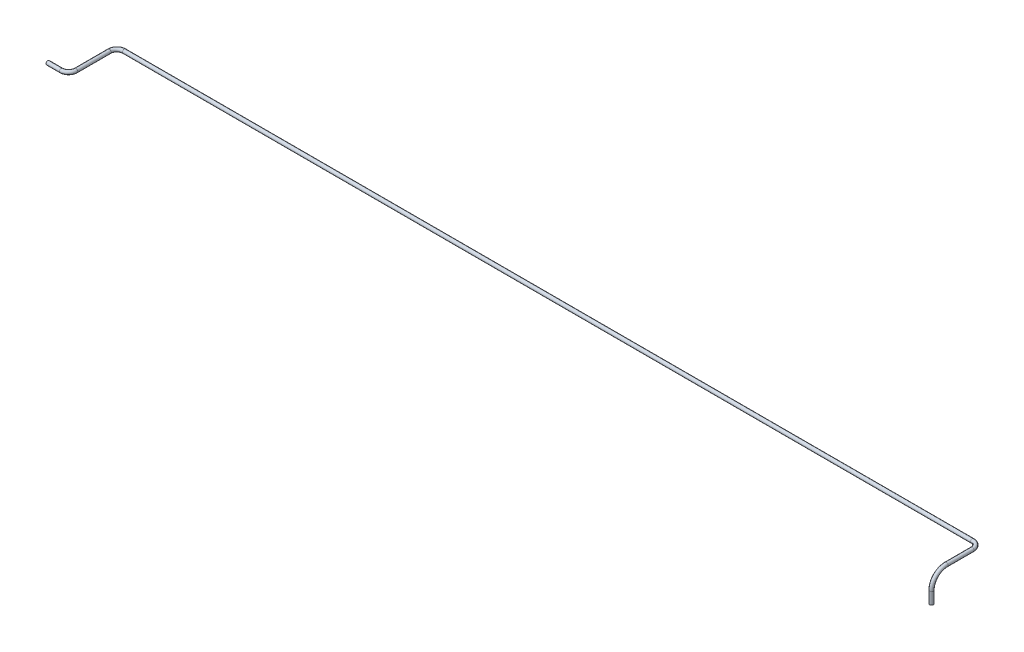
SolidWorks part; units mm, degrees
ref_plane "Front Plane" through (0, 0, 0) normal (0, 0, 1) x (1, 0, 0)
ref_plane "Top Plane" through (0, 0, 0) normal (0, 1, 0) x (1, 0, 0)
ref_plane "Right Plane" through (0, 0, 0) normal (1, 0, 0) x (0, 0, -1)
sketch3d "3DSketch1"
  line L1 (0, 0, 0) -> (22.86, 0, 0)
  line L2 (35.56, 0, -12.7) -> (35.56, 0, -69.85)
  line L3 (48.26, 0, -82.55) -> (1499.6587, 0, -82.55)
  line L4 (1512.3587, 0, -69.85) -> (1512.3587, 0, -25.4)
  line L5 (1512.3587, -25.4, 0) -> (1512.3587, -45.72, 0)
  arc A0 (1512.3587, 0, -69.85) -> (1499.6587, 0, -82.55) centre (1499.6587, 0, -69.85) ccw
  arc A1 (35.56, 0, -69.85) -> (48.26, 0, -82.55) centre (48.26, 0, -69.85) ccw
  arc A2 (22.86, 0, 0) -> (35.56, 0, -12.7) centre (22.86, 0, -12.7) ccw
  arc A3 (1512.3587, 0, -25.4) -> (1512.3587, -25.4, 0) centre (1512.3587, -25.4, -25.4) ccw
  point P9 (1512.3587, 0, -82.55)
  point P10 (1499.6587, 12.7, -69.85)
  point P12 (1512.3587, 0, 0)
  point P16 (35.56, 0, -82.55)
  point P17 (48.26, -12.7, -69.85)
  point P20 (35.56, 0, 0)
  point P22 (22.86, 12.7, -12.7)
  point P23 (1537.7587, -25.4, -25.4)
  dimension "D6" = 12.7
  dimension "D7" = 12.7
  dimension "D8" = 25.4
  dimension "D1" = 35.56
  dimension "D2" = 82.55
  dimension "D3" = 1476.7987
  dimension "D4" = 82.55
  dimension "D5" = 45.72
ref_plane "Plane4" through (0, 0, 0) normal (1, 0, 0) x (0, 0, -1)
sketch "Sketch5" plane through (0, 0, 0) normal (1, 0, 0) x (0, 0, -1)
  circle A0 centre (0, 0) radius 3.175
  circle A1 centre (0, 0) radius 2.667
  dimension "D1" = 6.35
  dimension "D2" = 0.508
sweep "Sweep3" add profiles "Sketch5" path "3DSketch1"
